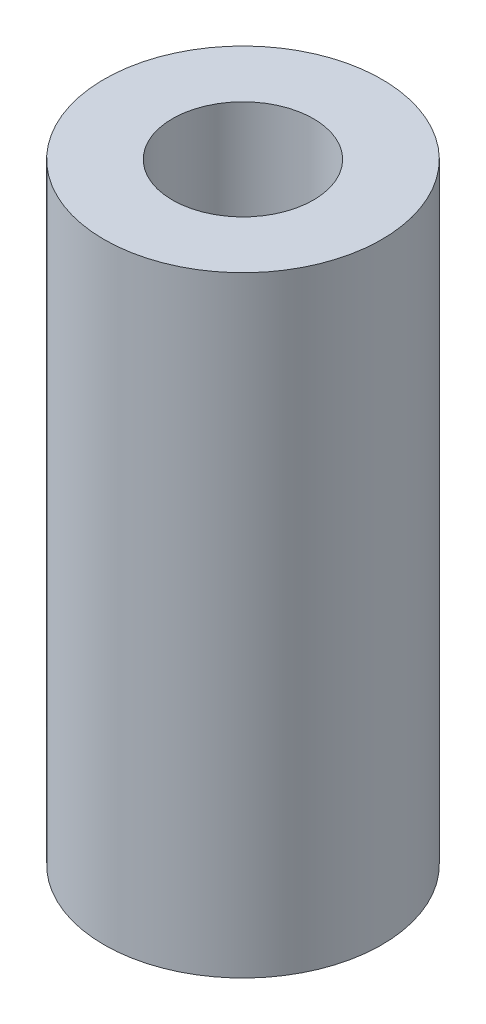
SolidWorks part; units mm, degrees
ref_plane "Front Plane" through (0, 0, 0) normal (0, 0, 1) x (1, 0, 0)
ref_plane "Top Plane" through (0, 0, 0) normal (0, 1, 0) x (1, 0, 0)
ref_plane "Right Plane" through (0, 0, 0) normal (1, 0, 0) x (0, 0, -1)
sketch "Sketch1" plane through (0, 0, 0) normal (0, 1, 0) x (1, 0, 0)
  circle A0 centre (0, 0) radius 6.35
  arc A4 (5.8179, -2.5444) -> (-4.3575, 4.6189) centre (0, 0) ccw construction
  circle A5 centre (0, 0) radius 3.2258
  circle A6 centre (0, 0) radius 3.2258
  dimension "D1" = 0.0508
extrude "Boss-Extrude1" add sketch "Sketch1" along normal up to surface (27.9373 mm away)
